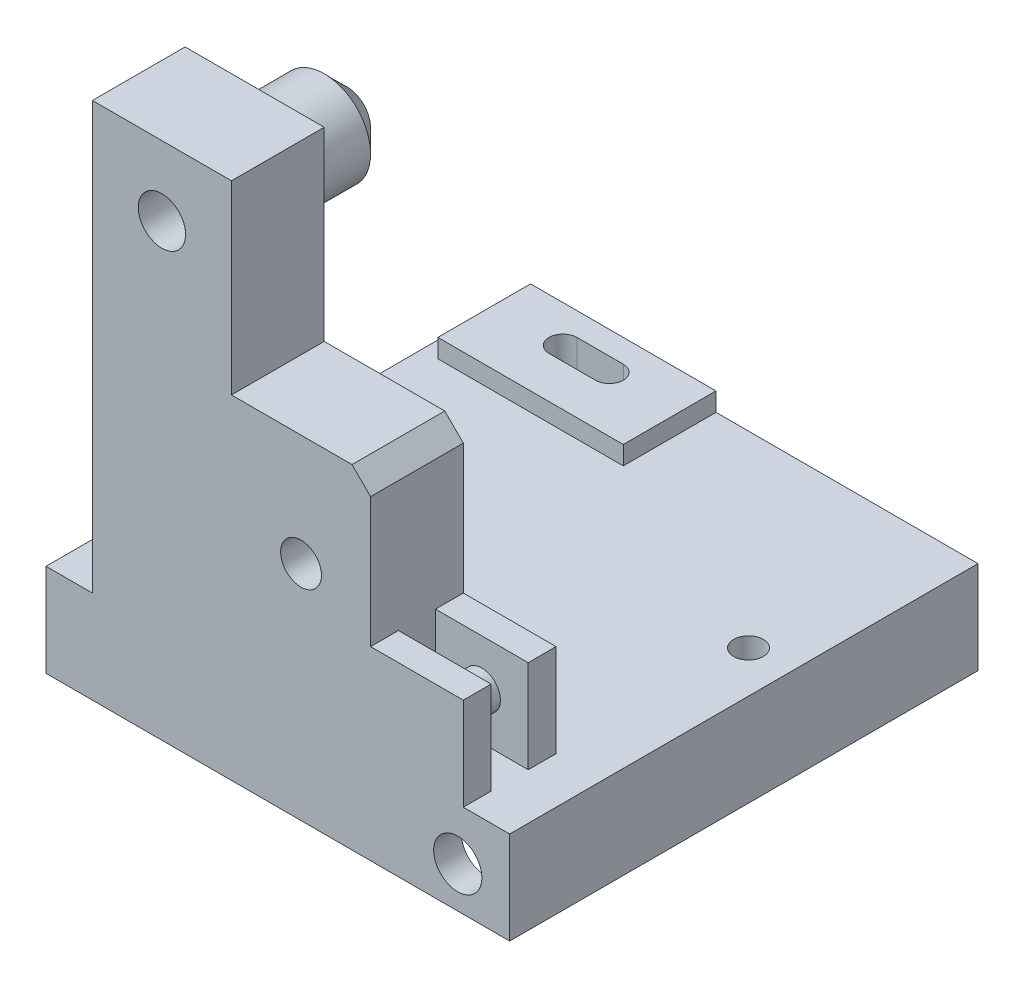
SolidWorks part; units mm, degrees
ref_plane "Front Plane" through (0, 0, 0) normal (0, 0, 1) x (1, 0, 0)
ref_plane "Top Plane" through (0, 0, 0) normal (0, 1, 0) x (1, 0, 0)
ref_plane "Right Plane" through (0, 0, 0) normal (1, 0, 0) x (0, 0, -1)
sketch "Sketch1" plane through (0, 0, 0) normal (0, 0, 1) x (1, 0, 0)
  line L0 (-15, 0) -> (-15, 46)
  line L1 (-15, 46) -> (0, 46)
  line L2 (0, 46) -> (0, 26)
  line L5 (0, 26) -> (15, 26)
  line L6 (15, 26) -> (15, 0)
  line L12 (-15, 0) -> (15, 0)
  circle A0 centre (-7.5, 38.5) radius 2.55
  circle A1 centre (7.5, 14) radius 2.2
  point P8 (0, 0)
  point P12 (-7.5, 46)
  point P16 (7.5, 26)
  dimension "D7" = 5.1
  dimension "D9" = 4.4
  dimension "D1" = 46
  dimension "D2" = 15
  dimension "D3" = 30
  dimension "D6" = 20
  dimension "D8" = 7.5
  dimension "D10" = 12
extrude "Boss-Extrude1" add sketch "Sketch1" along normal blind 6 and the other way blind 4
sketch "Sketch2" plane through (15, 0, 0) normal (1, 0, 0) x (0, 0, -1)
  line L0 (-6, 0) -> (4, 0) construction
  line L1 (-6, 0) -> (-6, 26) construction
  circle A0 centre (-1, 5) radius 2.5
  dimension "D1" = 5
  dimension "D2" = 5
  dimension "D3" = 5
extrude "Boss-Extrude2" [suppressed] add sketch "Sketch2" along normal blind 6
sketch "Sketch3" [suppressed] plane through (21, 0, 0) normal (1, 0, 0) x (0, 0, -1)
  circle A0 centre (-5, 5) radius 4.5
  circle A1 centre (-5, 5) radius 2.5
  circle A2 centre (-5, 5) radius 2.5 construction
  dimension "D1" = 0
  dimension "D2" = 2
extrude "Boss-Extrude3" [suppressed] add sketch "Sketch3" along normal blind 2
ref_plane "Plane1" through (0, 0, -4) normal (0, 0, -1) x (-1, 0, 0)
sketch "Sketch4" plane through (0, 0, -4) normal (0, 0, -1) x (-1, 0, 0)
  line L0 (-15, 0) -> (-15, 10)
  line L1 (-15, 0) -> (-25, 0)
  line L2 (-15, 10) -> (-25, 10)
  line L3 (-25, 0) -> (-25, 10)
  line L4 (-15, 0) -> (-15, 26) construction
  dimension "D1" = 10
  dimension "D2" = 10
extrude "Boss-Extrude4" add sketch "Sketch4" against normal blind 10
sketch "Sketch5" plane through (25, 0, 0) normal (1, 0, 0) x (0, 0, -1)
  line L0 (-3, 10) -> (1, 10)
  line L1 (-3, 10) -> (-3, 0)
  line L2 (1, 10) -> (1, 0)
  line L3 (-3, 0) -> (1, 0)
  line L4 (-6, 10) -> (4, 10) construction
  line L5 (-6, 0) -> (4, 0) construction
  line L7 (-6, 10) -> (4, 10) construction
  point P8 (-1, 10)
  dimension "D1" = 4
extrude "Cut-Extrude1" cut sketch "Sketch5" against normal up to surface (10 mm away) up to face at (15, 18, 1)
sketch "Sketch6" plane through (0, 0, -1) normal (0, 0, 1) x (1, 0, 0)
  line L0 (25, 10) -> (25, 0) construction
  line L1 (15, 10) -> (25, 10) construction
  circle A0 centre (20, 5) radius 2
  dimension "D1" = 4
  dimension "D2" = 5
  dimension "D3" = 5
extrude "Boss-Extrude5" add sketch "Sketch6" along normal up to next
fillet "Fillet1" [suppressed] radius 2
chamfer "Chamfer1" distance 2 angle 45 1 edges at (15, 26, 1)
sketch "Sketch7" plane through (0, 0, 0) normal (0, -1, 0) x (1, 0, 0)
  line L1 (25, 6) -> (-15, 6) construction
  line L2 (25, 6) -> (25, -9.5) construction
  line L3 (25, -9.5) -> (-15, -9.5) construction
  line L4 (-15, 6) -> (-15, -9.5) construction
  line L5 (-15, 6) -> (-15, -4) construction
  line L12 (30, -14.5) -> (-20, -14.5)
  line L24 (-16.5, -4) -> (16.5, -4) construction
  line L32 (30, 11) -> (-20, 11) construction
  line L33 (-20, 11) -> (-20, -14.5) construction
  line L34 (30, 11) -> (30, -14.5) construction
  line L35 (-20, -14.5) -> (-20, 6)
  line L36 (-20, 6) -> (30, 6)
  line L37 (30, 6) -> (30, -14.5)
  line L38 (-15, 6) -> (25, 6) construction
  dimension "D2" = 5.5
  dimension "D1" = 5
extrude "Boss-Extrude6" add sketch "Sketch7" along normal blind 10
sketch "Sketch12" plane through (0, 0, 0) normal (0, 1, 0) x (1, 0, 0)
  line L0 (-15, 4) -> (25, 4) construction
  line L3 (-20, 10) -> (-2.5, 10) construction
  line L4 (-20, -6) -> (-20, 14.5) construction
  line L5 (-10.75, 11.5) -> (-5.75, 11.5)
  line L6 (-10.75, 8.5) -> (-5.75, 8.5)
  circle A2 centre (-8.25, 10) radius 1.5 construction
  arc A3 (-10.75, 11.5) -> (-10.75, 8.5) centre (-10.75, 10) ccw
  arc A4 (-5.75, 11.5) -> (-5.75, 8.5) centre (-5.75, 10) cw
  point P12 (-8.25, 8.5)
  point P13 (-8.25, 11.5)
  point P14 (-11.25, 10)
  dimension "D1" = 3
  dimension "D2" = 3
  dimension "D3" = 17.5
  dimension "D4" = 6
  dimension "D5" = 5
sketch "Sketch13" plane through (0, 0, -14.5) normal (0, 0, -1) x (-1, 0, 0)
  line L1 (-30, 0) -> (20, 0)
  line L2 (-30, 0) -> (-30, -10)
  line L3 (-30, -10) -> (20, -10)
  line L4 (20, 0) -> (20, -10)
extrude "Boss-Extrude9" add sketch "Sketch13" along normal blind 30
sketch "Sketch14" plane through (0, 0, 0) normal (0, 1, 0) x (1, 0, 0)
  line L0 (-20, 24.25) -> (30, 24.25) construction
  line L3 (30, 44.5) -> (30, -6) construction
  line L4 (-20, -6) -> (-20, 44.5) construction
  line L7 (0, 4) -> (-15, 4) construction
  dimension "D1" = 20.25
ref_plane "Plane2" through (0, 0, -24.25) normal (0, 0, -1) x (-1, 0, 0)
sketch "Sketch16" plane through (0, -10, 0) normal (0, -1, 0) x (1, 0, 0)
  line L8 (27, -41.5) -> (27, 3)
  line L9 (27, -41.5) -> (27, 3)
  line L10 (-17, -41.5) -> (27, -41.5)
  line L11 (27, 3) -> (-17, 3)
  line L14 (-17, -41.5) -> (27, -41.5)
  line L16 (27, 3) -> (-17, 3)
  line L17 (-17, 3) -> (-17, -41.5)
  line L18 (-17, 3) -> (-17, -41.5)
  dimension "D1" = 3
extrude "Cut-Extrude3" cut sketch "Sketch16" against normal blind 7
sketch "Sketch17" plane through (0, 0, 6) normal (0, 0, 1) x (1, 0, 0)
  line L1 (-20, 0) -> (30, 0) construction
  line L2 (30, -10) -> (30, 0) construction
  circle A0 centre (24.4, -5.6) radius 2.6
  dimension "D1" = 5.2
  dimension "D2" = 5.6
  dimension "D3" = 5.6
extrude "Cut-Extrude4" cut sketch "Sketch17" against normal up to surface (3 mm away) up to face at (5, -6.5, 3)
sketch "Sketch18" plane through (-20, 0, 0) normal (-1, 0, 0) x (0, 0, 1)
  line L1 (-9, -10) -> (-11, -10)
  line L2 (-9, -10) -> (-9, 0)
  line L3 (-9, 0) -> (-11, 0)
  line L4 (-11, -10) -> (-11, 0)
  line L6 (-44.5, -10) -> (-44.5, 0) construction
  line L7 (6, 0) -> (-44.5, 0) construction
  line L8 (6, -10) -> (-44.5, -10) construction
  dimension "D1" = 2
  dimension "D2" = 33.5
extrude "Boss-Extrude11" add sketch "Sketch18" along normal blind 5
fillet "Fillet2" radius 5 1 edges at (-20, -5, -11)
ref_plane "Plane3" through (-7.5, 0, 0) normal (1, 0, 0) x (0, 0, -1)
sketch "Sketch19" plane through (-7.5, 0, 0) normal (-1, 0, 0) x (0, 0, 1)
  line L0 (-4, 38.5) -> (-14, 38.5)
  line L1 (-4, 46) -> (-4, 0) construction
  line L2 (-11.5, 43.5) -> (-4, 43.5)
  line L3 (-4, 43.5) -> (-4, 38.5)
  line L4 (-4, 46) -> (6, 46) construction
  line L5 (-14, 38.5) -> (-14, 41)
  line L6 (-11.5, 43.5) -> (-14, 41)
  dimension "D2" = 135
  dimension "D1" = 7.5
  dimension "D3" = 10
  dimension "D4" = 5
  dimension "D5" = 2.5
revolve "Revolve1" add sketch "Sketch19" angle 360 about L0
sketch "Sketch20" plane through (0, 0, -4) normal (0, 0, 1) x (1, 0, 0)
  circle A1 centre (-7.5, 38.5) radius 2.55
  circle A2 centre (-7.5, 38.5) radius 2.55
  dimension "D1" = 0
extrude "Cut-Extrude5" cut sketch "Sketch20" against normal up to next
fillet "Fillet5" radius 1.5 1 edges at (-12.5, 38.5, -4)
extrude "Cut-Extrude6" cut sketch "Sketch12" against normal blind 3 contours A4 L6 A3 L5
sketch "Sketch22" plane through (0, 0, 0) normal (0, 1, 0) x (1, 0, 0)
  line L0 (22, 4) -> (-22, 4) construction
  line L1 (-18.25, 14) -> (1.75, 14)
  line L2 (-18.25, 14) -> (-18.25, 4)
  line L3 (-18.25, 4) -> (1.75, 4)
  line L4 (1.75, 14) -> (1.75, 4)
  line L5 (-8.25, 4) -> (-8.25, 14) construction
  line L6 (-10.75, 8.5) -> (-5.75, 8.5) construction
  line L7 (-10.75, 11.5) -> (-5.75, 11.5) construction
  line L8 (-10.75, 8.5) -> (-5.75, 8.5)
  line L9 (-10.75, 11.5) -> (-5.75, 11.5)
  arc A2 (-5.75, 8.5) -> (-5.75, 11.5) centre (-5.75, 10) ccw construction
  arc A3 (-10.75, 11.5) -> (-10.75, 8.5) centre (-10.75, 10) ccw construction
  arc A4 (-5.75, 8.5) -> (-5.75, 11.5) centre (-5.75, 10) ccw
  arc A5 (-10.75, 11.5) -> (-10.75, 8.5) centre (-10.75, 10) ccw
  point P15 (-8.25, 11.5)
  dimension "D1" = 20
  dimension "D2" = 10
extrude "Boss-Extrude12" add sketch "Sketch22" along normal blind 2
mirror "Mirror2" [suppressed] about plane through (0, 0, -24.25) normal (0, 0, -1)
pattern_linear "LPattern1" count 2 spacing 30.5 along (0, 0, -1) of "Boss-Extrude12", "Cut-Extrude6"
sketch "Sketch23" plane through (0, 0, 0) normal (0, 1, 0) x (1, 0, 0)
  line L0 (-20, 24.25) -> (30, 24.25) construction
  line L1 (30, 44.5) -> (30, -6) construction
  circle A0 centre (25.5, 24.25) radius 1.6
  dimension "D1" = 3.2
  dimension "D2" = 4.5
extrude "Cut-Extrude7" cut sketch "Sketch23" against normal up to next
